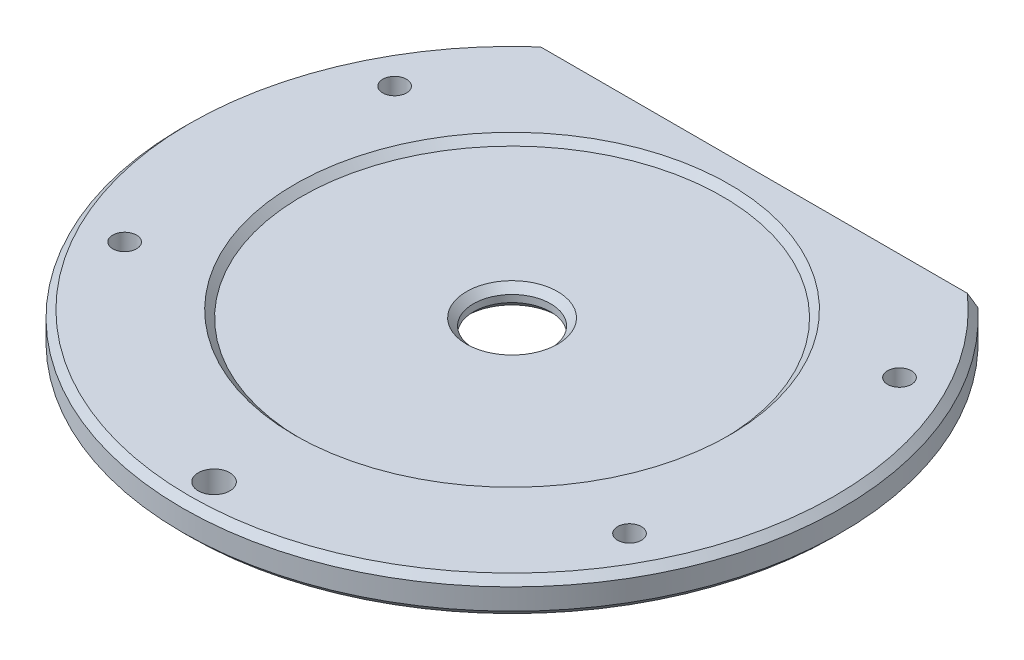
SolidWorks part; units mm, degrees
ref_plane "前视基准面" through (0, 0, 0) normal (0, 0, 1) x (1, 0, 0)
ref_plane "上视基准面" through (0, 0, 0) normal (0, 1, 0) x (1, 0, 0)
ref_plane "右视基准面" through (0, 0, 0) normal (1, 0, 0) x (0, 0, -1)
sketch "草图2" plane through (0, 0, 0) normal (0, 1, 0) x (1, 0, 0)
  circle A0 centre (0, 0) radius 94
  dimension "D1" = 188
extrude "凸台-拉伸1" add sketch "草图2" along normal mid plane 10
sketch "草图3" plane through (0, 5, 0) normal (0, 1, 0) x (1, 0, 0)
  line L0 (0, 94) -> (65.8408, 94) construction
  line L1 (-96.2922, 94) -> (108.2259, 94)
  line L2 (-96.2922, 94) -> (-96.2922, 69)
  line L3 (-96.2922, 69) -> (108.2259, 69)
  line L4 (108.2259, 94) -> (108.2259, 69)
  circle A0 centre (0, 0) radius 94 construction
  dimension "D1" = 69
extrude "切除-拉伸1" cut sketch "草图3" against normal through all
sketch "草图4" plane through (0, 5, 0) normal (0, 1, 0) x (1, 0, 0)
  circle A0 centre (0, 0) radius 11
  dimension "D1" = 22
extrude "切除-拉伸2" cut sketch "草图4" against normal through all
sketch "草图5" plane through (0, 5, 0) normal (0, 1, 0) x (1, 0, 0)
  circle A0 centre (0, 0) radius 60
  dimension "D1" = 120
extrude "切除-拉伸3" cut sketch "草图5" against normal blind 2
mirror "镜向1" about plane through (0, 0, 0) normal (0, 1, 0) of "切除-拉伸3"
hole_wizard "M8x1.25 螺纹孔1" positions "草图7" profile "草图6" tap size "M8x1.25" standard "JIS"
sketch "草图7" plane through (0, 5, 0) normal (0, 1, 0) x (-1, 0, 0)
  line L0 (0, 0) -> (0, -81.8991) construction
  line L2 (0, 0) -> (-84.1415, 0) construction
  point P1 (72, -38.5)
  point P11 (-72, -38.5)
  point P17 (72, 38.5)
  point P18 (-72, 38.5)
  dimension "D1" = 144
  dimension "D2" = 77
sketch "草图6" plane through (-72, 5, -38.5) normal (1, 0, 0) x (0, 0, 1)
  line L0 (0, 0) -> (0, 21.7929)
  line L1 (0, 21.7929) -> (3.4, 19.75)
  line L2 (3.4, 19.75) -> (3.4, 0)
  line L5 (3.4, 0) -> (0, 0)
  line L10 (0, 21.7929) -> (-3.4, 19.75) construction
  line L11 (0, -6.35) -> (0, 107.95) construction
  dimension "螺纹孔钻头直径" = 6.8
  dimension "螺纹孔钻头深度" = 19.75
  dimension "导头角度" = 118
cosmetic thread "孔螺蚊线1" parameters "D1"=10, "D2"=8
cosmetic thread "孔螺蚊线2" parameters "D1"=10, "D2"=8
cosmetic thread "孔螺蚊线3" parameters "D1"=10, "D2"=8
cosmetic thread "孔螺蚊线4" parameters "D1"=10, "D2"=8
sketch "草图8" plane through (0, 5, 0) normal (0, 1, 0) x (1, 0, 0)
  line L0 (0, 0) -> (0, -85) construction
  circle A0 centre (0, -85) radius 4.5
  dimension "D2" = 9
  dimension "D1" = 85
extrude "切除-拉伸4" cut sketch "草图8" against normal through all
chamfer "倒角1" distance 2 angle 45 6 edges at (0, 3, 11) (0, -3, -11) (0, -5, 60) (0, 5, 60) (0, -5, 94) (0, 5, 94)
